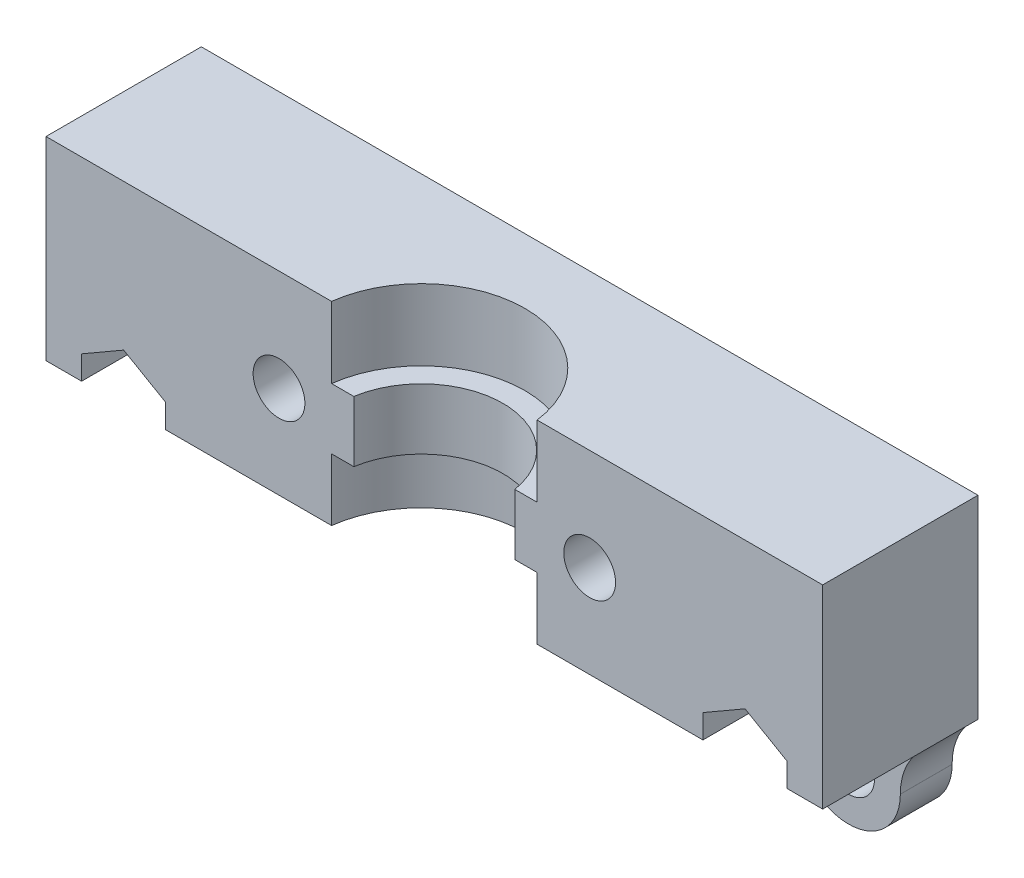
SolidWorks part; units mm, degrees
ref_plane "Piano frontale" through (0, 0, 0) normal (0, 0, 1) x (1, 0, 0)
ref_plane "Piano superiore" through (0, 0, 0) normal (0, 1, 0) x (1, 0, 0)
ref_plane "Piano destro" through (0, 0, 0) normal (1, 0, 0) x (0, 0, -1)
sketch "Schizzo1" plane through (0, 0, 0) normal (0, 0, 1) x (1, 0, 0)
  line L1 (-30, 15) -> (30, 15)
  line L2 (-30, 15) -> (-30, -15)
  line L3 (-30, -15) -> (30, -15)
  line L4 (30, 15) -> (30, -15)
  line L5 (-30, 15) -> (30, -15) construction
  line L6 (-30, -15) -> (30, 15) construction
  point P0 (0, 0)
  dimension "D1" = 60
  dimension "D2" = 30
extrude "Estrusione-Estrusione1" add sketch "Schizzo1" along normal blind 5
sketch "Schizzo2" plane through (0, 0, 5) normal (0, 0, 1) x (1, 0, 0)
  line L0 (-32.3459, -15) -> (49.5432, -15) construction
  line L1 (-32.3459, -8) -> (49.5432, -8) construction
  line L3 (30, -15) -> (30, 15) construction
  line L4 (-30, 15) -> (30, 15)
  line L5 (-30, 15) -> (-30, 7)
  line L6 (-30, 7) -> (30, 7)
  line L7 (30, 15) -> (30, 7)
  dimension "D1" = 7
extrude "Estrusione-Estrusione2" add sketch "Schizzo2" along normal blind 20
sketch "Schizzo3" plane through (0, 15, 0) normal (0, 1, 0) x (1, 0, 0)
  line L0 (0, 7.3603) -> (0, -33.3603) construction
  line L1 (11, 7.3603) -> (11, -33.3603) construction
  line L2 (30, 0) -> (-30, 0) construction
  circle A0 centre (11, -13) radius 5
  circle A1 centre (-11, -13) radius 5
  dimension "D2" = 10
  dimension "D3" = 13
  dimension "D1" = 11
extrude "Taglio-Estrusione1" cut sketch "Schizzo3" against normal up to surface (8 mm away) up to face at (-7.5, 7, 20)
fillet "Raccordo1" radius 20 2 edges at (30, 11, 25) (-30, 11, 25)
sketch "Schizzo4" plane through (0, 0, 5) normal (0, 0, 1) x (1, 0, 0)
  line L0 (-30, 7) -> (30, 7) construction
  line L1 (-30, 7) -> (30, 7)
  line L2 (-30, -8) -> (30, -8)
  line L3 (-30, -8) -> (-30, 7)
  line L4 (30, -8) -> (30, 7)
  dimension "D1" = 15
extrude "Estrusione-Estrusione3" add sketch "Schizzo4" along normal blind 10
sketch "Schizzo6" plane through (0, -8, 0) normal (0, -1, 0) x (1, 0, 0)
  line L0 (0, 28.7661) -> (0, -12.0233) construction
  line L1 (0, -7.3603) -> (0, 33.3603) construction
  line L2 (-11, 13) -> (0, 13) construction
  circle A0 centre (0, 13) radius 8
  dimension "D1" = 16
extrude "Taglio-Estrusione2" cut sketch "Schizzo6" against normal blind 15
ref_plane "Piano1" through (-30, 7, 15) normal (0, -1, 0) x (-1, 0, 0)
sketch "Schizzo8" plane through (0, 0, 15) normal (0, 0, 1) x (1, 0, 0)
  line L1 (-30, 1.5) -> (-30, -3.2)
  line L3 (30, 1.5) -> (30, -3.2)
  line L4 (-30, 1.5) -> (30, 1.5)
  line L5 (-30, -3.2) -> (30, -3.2)
  line L8 (-31.6659, 1.5) -> (35.7067, 1.5) construction
  line L9 (-31.6659, -3.2) -> (35.7067, -3.2) construction
  dimension "D3" = 4.7
extrude "Estrusione-Estrusione4" add sketch "Schizzo8" against normal up to surface (10 mm away) up to face at (0, -10.8, 5)
sketch "Schizzo9" plane through (0, -3.2, 0) normal (0, -1, 0) x (1, 0, 0)
  line L0 (0, 27.458) -> (0, -16.0891) construction
  line L1 (0, -7.3603) -> (0, 33.3603) construction
  line L2 (-11, 13) -> (0, 13) construction
  circle A0 centre (0, 13) radius 6.3
extrude "Taglio-Estrusione3" cut sketch "Schizzo9" against normal blind 5
sketch "Schizzo10" plane through (0, 0, 15) normal (0, 0, 1) x (1, 0, 0)
  line L0 (-31.0418, -0.85) -> (32.2221, -0.85) construction
  line L1 (0, -0.85) -> (0, 7.0573) construction
  circle A1 centre (12, -0.85) radius 2
  circle A2 centre (-12, -0.85) radius 2
  dimension "D1" = 12
  dimension "D2" = 12
extrude "Taglio-Estrusione4" cut sketch "Schizzo10" against normal through all
sketch "Schizzo11" plane through (0, 0, 0) normal (0, 0, -1) x (-1, 0, 0)
  line L1 (-30, 15) -> (30, 15)
  line L2 (-30, 15) -> (-30, 7)
  line L3 (-30, 7) -> (30, 7)
  line L4 (30, 15) -> (30, 7)
extrude "Taglio-Estrusione5" cut sketch "Schizzo11" against normal blind 25
sketch "Schizzo14" plane through (0, -15, 0) normal (0, -1, 0) x (1, 0, 0)
  line L1 (-30, 0) -> (30, 0)
  line L2 (-30, 0) -> (-30, 5)
  line L3 (-30, 5) -> (30, 5)
  line L4 (30, 0) -> (30, 5)
extrude "Taglio-Estrusione7" cut sketch "Schizzo14" against normal up to surface (7 mm away) up to face at (17.5494, -8, 9.5253)
sketch "Schizzo12" plane through (0, 0, 0) normal (0, 0, 1) x (1, 0, 0)
  line L0 (-8, -8.0064) -> (8, -8.0064)
  line L21 (-28, -12.0064) -> (-28, -5.2564)
  line L22 (28, -12.0064) -> (28, -5.2564)
  line L23 (8, -8.0064) -> (20, -8.0064)
  line L24 (20, -12.0064) -> (20, -8.0064)
  line L27 (-20, -12.0064) -> (-20, -8.0064)
  line L28 (-20, -8.0064) -> (-8, -8.0064)
  line L29 (-28, -5.2564) -> (28, -5.2564)
  arc A8 (20, -12.0064) -> (28, -12.0064) centre (24, -12.0064) ccw
  arc A11 (-20, -12.0064) -> (-28, -12.0064) centre (-24, -12.0064) cw
  circle A12 centre (24, -12.0064) radius 2
  circle A13 centre (-24, -12.0064) radius 2
  point P3 (-59.4844, 2.75)
  point P4 (-3.4844, 2.75)
extrude "Estrusione-Estrusione5" add sketch "Schizzo12" along normal blind 4
sketch "Schizzo17" plane through (0, 0, 15) normal (0, 0, 1) x (1, 0, 0)
  line L1 (30, 7) -> (-30, 7)
  line L2 (30, 7) -> (30, -8)
  line L3 (30, -8) -> (-30, -8)
  line L4 (-30, 7) -> (-30, -8)
extrude "Taglio-Estrusione9" cut sketch "Schizzo17" against normal blind 3
sketch "Schizzo18" plane through (0, 0, 0) normal (0, 0, -1) x (-1, 0, 0)
  line L0 (0, 7) -> (0, -29.2388) construction
  line L1 (30, 7) -> (-30, 7) construction
  line L2 (-25.4648, -13.3682) -> (-18.017, -6.444) construction
  line L3 (-26, -8.0431) -> (-26, -12.0064)
  line L4 (-26, -12.0064) -> (-22, -12.0064)
  line L5 (-22, -12.0064) -> (-22, -8.0431)
  line L6 (22, -12.0064) -> (22, -8.0431)
  line L7 (26, -12.0064) -> (22, -12.0064)
  line L8 (26, -8.0431) -> (26, -12.0064)
  circle A0 centre (-24, -12.0064) radius 2 construction
  arc A1 (-22, -8.0431) -> (-26, -8.0431) centre (-24, -8.0431) ccw
  arc A2 (22, -8.0431) -> (26, -8.0431) centre (24, -8.0431) cw
  point P21 (-52.0955, -3.6608)
extrude "Taglio-Estrusione10" cut sketch "Schizzo18" against normal up to surface (12 mm away) up to face at (-14, -0.85, 12)
sketch "Schizzo19" plane through (0, 0, 12) normal (0, 0, 1) x (1, 0, 0)
  line L0 (-24, -6.0431) -> (-24, -8.0431) construction
  line L1 (-24, -8.0431) -> (-22, -8.0431) construction
  arc A1 (-22.0005, -8) -> (-25.9995, -8) centre (-24, -8.0431) ccw construction
sketch "Schizzo20" plane through (0, 0, 4) normal (0, 0, 1) x (1, 0, 0)
  line L0 (-27.25, -9.9195) -> (-24, -11.7959)
  line L7 (-24, -11.7959) -> (-20.75, -9.9195)
  line L8 (-20.75, -9.9195) -> (-20.75, -6.1667)
  line L9 (-20.75, -6.1667) -> (-24, -4.2903)
  line L10 (-24, -4.2903) -> (-27.25, -6.1667)
  line L11 (-27.25, -6.1667) -> (-27.25, -9.9195)
extrude "Taglio-Estrusione12" cut sketch "Schizzo20" along normal up to surface (8 mm away) up to face at (10, -0.85, 12)
mirror "Specchia1" about plane through (0, 0, 0) normal (1, 0, 0) of "Taglio-Estrusione12"
fillet "Raccordo2" radius 5 2 edges at (28, -8, 2) (-28, -8, 2)
fillet "Raccordo3" radius 10 2 edges at (-20, -8.0064, 2) (20, -8.0064, 2)
